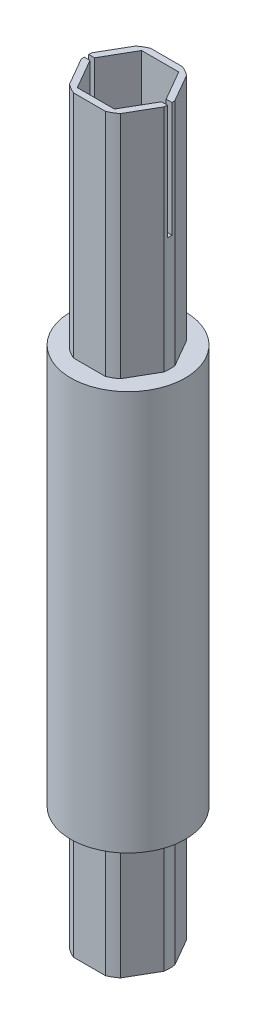
SolidWorks part; units mm, degrees
material "PET"
ref_plane "Front Plane" through (0, 0, 0) normal (0, 0, 1) x (1, 0, 0)
ref_plane "Top Plane" through (0, 0, 0) normal (0, 1, 0) x (1, 0, 0)
ref_plane "Right Plane" through (0, 0, 0) normal (1, 0, 0) x (0, 0, -1)
sketch "Sketch1" plane through (0, 0, 0) normal (0, 1, 0) x (1, 0, 0)
  line L1 (6.8647, 0.9115) -> (4.2218, 5.4893)
  line L2 (2.643, 6.4008) -> (-2.643, 6.4008)
  line L3 (-4.2218, 5.4893) -> (-6.8647, 0.9115)
  line L4 (-6.8647, -0.9115) -> (-4.2218, -5.4893)
  line L5 (-2.643, -6.4008) -> (2.643, -6.4008)
  line L6 (4.2218, -5.4893) -> (6.8647, -0.9115)
  circle A0 centre (0, 0) radius 6.4008 construction
  arc A1 (-2.643, 6.4008) -> (-4.2218, 5.4893) centre (0, 0) ccw
  arc A2 (4.2218, 5.4893) -> (2.643, 6.4008) centre (0, 0) ccw
  arc A3 (6.8647, -0.9115) -> (6.8647, 0.9115) centre (0, 0) ccw
  arc A4 (2.643, -6.4008) -> (4.2218, -5.4893) centre (0, 0) ccw
  arc A5 (-4.2218, -5.4893) -> (-2.643, -6.4008) centre (0, 0) ccw
  arc A6 (-6.8647, 0.9115) -> (-6.8647, -0.9115) centre (0, 0) ccw
  dimension "D1" = 12.8016
  dimension "D2" = 13.85
extrude "Boss-Extrude1" add sketch "Sketch1" against normal blind 19.812
sketch "Sketch2" plane through (0, 0, 0) normal (0, -1, 0) x (-1, 0, 0)
  circle A0 centre (0, 0) radius 9.5
  dimension "D1" = 19
extrude "Boss-Extrude2" add sketch "Sketch2" against normal blind 66.294
extrude "Boss-Extrude6" add sketch "Sketch1<4>" along normal blind 104.394
sketch "Sketch1<4>" plane through (0, 0, 0) normal (0, 1, 0) x (1, 0, 0) same geometry as "Sketch1"
sketch "Sketch6" plane through (0, 104.394, 0) normal (0, 1, 0) x (1, 0, 0)
  line L1 (-6.925, 0.381) -> (6.925, 0.381)
  line L2 (-6.925, 0.381) -> (-6.925, -0.381)
  line L3 (-6.925, -0.381) -> (6.925, -0.381)
  line L4 (6.925, 0.381) -> (6.925, -0.381)
  line L5 (-6.925, 0.381) -> (6.925, -0.381) construction
  line L6 (-6.925, -0.381) -> (6.925, 0.381) construction
  arc A0 (6.8647, -0.9115) -> (6.8647, 0.9115) centre (0, 0) ccw construction
  point P0 (0, 0)
  dimension "D1" = 0.762
extrude "Cut-Extrude1" cut sketch "Sketch6" against normal blind 19.05
sketch "Sketch7" plane through (0, 104.394, 0) normal (0, 1, 0) x (1, 0, 0)
  line L1 (4.0415, 0) -> (2.0207, 3.5) construction
  line L2 (2.0207, 3.5) -> (-2.0207, 3.5) construction
  line L3 (-2.0207, 3.5) -> (-4.0415, 0) construction
  line L4 (-4.0415, 0) -> (-2.0207, -3.5) construction
  line L5 (-2.0207, -3.5) -> (2.0207, -3.5) construction
  line L6 (2.0207, -3.5) -> (4.0415, 0) construction
  line L8 (3.0796, 5.334) -> (-3.0796, 5.334)
  line L9 (-3.0796, 5.334) -> (-6.1592, 0)
  line L10 (-6.1592, 0) -> (-3.0796, -5.334)
  line L11 (-3.0796, -5.334) -> (3.0796, -5.334)
  line L12 (3.0796, -5.334) -> (6.1592, 0)
  line L13 (6.1592, 0) -> (3.0796, 5.334)
  circle A0 centre (0, 0) radius 3.5 construction
  circle A1 centre (0, 0) radius 5.334 construction
  dimension "D1" = 7
  dimension "D2" = 10.668
extrude "Cut-Extrude2" cut sketch "Sketch7" against normal blind 27.3977
